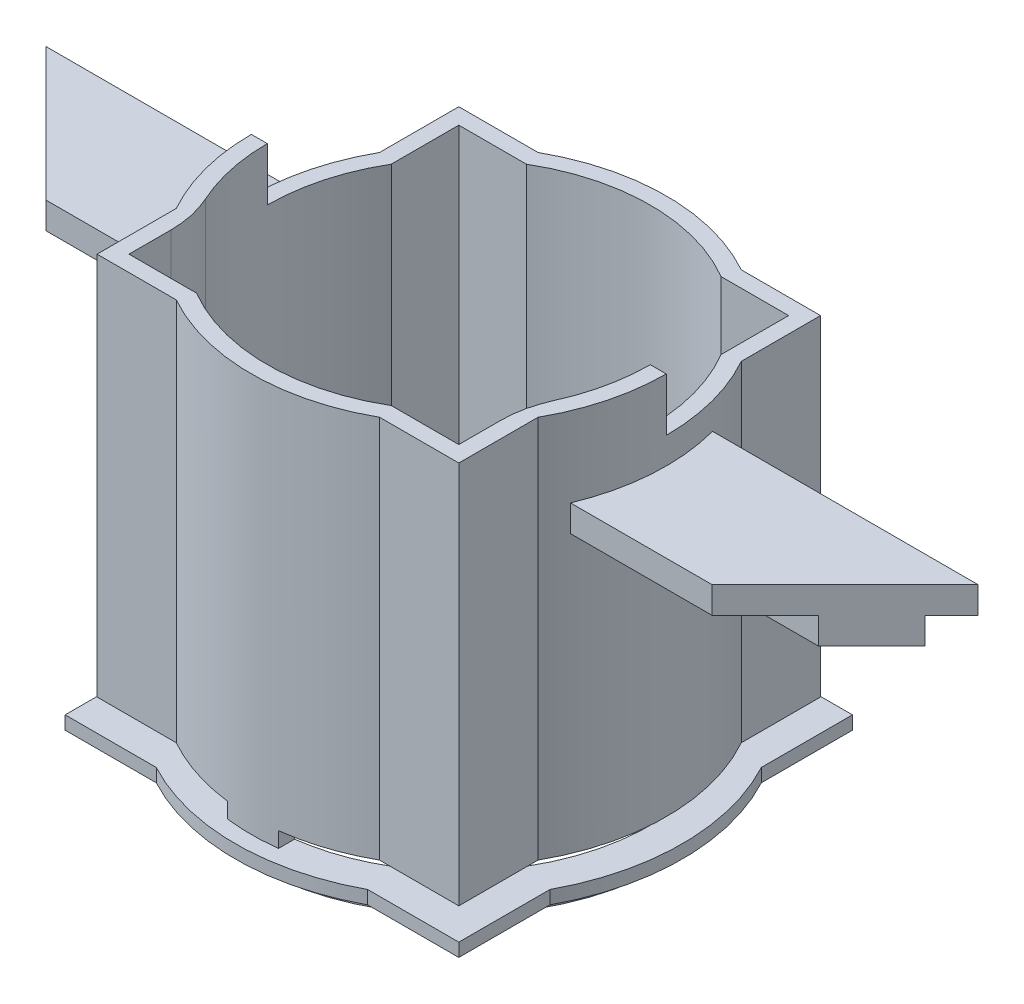
SolidWorks part; units mm, degrees
ref_plane "Front Plane" through (0, 0, 0) normal (0, 0, 1) x (1, 0, 0)
ref_plane "Top Plane" through (0, 0, 0) normal (0, 1, 0) x (1, 0, 0)
ref_plane "Right Plane" through (0, 0, 0) normal (1, 0, 0) x (0, 0, -1)
sketch "Sketch1" plane through (0, 0, 0) normal (0, 1, 0) x (1, 0, 0)
  line L0 (23.2448, 39.37) -> (39.37, 39.37)
  line L1 (-39.37, -39.37) -> (-23.2448, -39.37)
  line L2 (-39.37, -39.37) -> (-39.37, -23.2448)
  line L3 (-39.37, 39.37) -> (-23.2448, 39.37)
  line L4 (39.37, -39.37) -> (39.37, -23.2448)
  line L5 (-39.37, -39.37) -> (39.37, 39.37) construction
  line L6 (-39.37, 39.37) -> (39.37, -39.37) construction
  line L7 (39.37, 23.2448) -> (39.37, 39.37)
  line L8 (-39.37, 23.2448) -> (-39.37, 39.37)
  line L9 (23.2448, -39.37) -> (39.37, -39.37)
  line L10 (24.2633, 43.18) -> (43.18, 43.18)
  line L11 (43.18, 24.2633) -> (43.18, 43.18)
  line L12 (43.18, -43.18) -> (43.18, -24.2633)
  line L13 (24.2633, -43.18) -> (43.18, -43.18)
  line L14 (-43.18, -43.18) -> (-24.2633, -43.18)
  line L15 (-43.18, -43.18) -> (-43.18, -24.2633)
  line L16 (-43.18, 24.2633) -> (-43.18, 43.18)
  line L17 (-43.18, 43.18) -> (-24.2633, 43.18)
  arc A1 (-39.37, 23.2448) -> (-39.37, -23.2448) centre (0, 0) ccw
  arc A2 (23.2448, 39.37) -> (-23.2448, 39.37) centre (0, 0) ccw
  arc A3 (-23.2448, -39.37) -> (23.2448, -39.37) centre (0, 0) ccw
  arc A4 (39.37, -23.2448) -> (39.37, 23.2448) centre (0, 0) ccw
  arc A5 (43.18, -24.2633) -> (43.18, 24.2633) centre (0, 0) ccw
  arc A6 (-24.2633, -43.18) -> (24.2633, -43.18) centre (0, 0) ccw
  arc A7 (-43.18, 24.2633) -> (-43.18, -24.2633) centre (0, 0) ccw
  arc A8 (24.2633, 43.18) -> (-24.2633, 43.18) centre (0, 0) ccw
  point P0 (0, 0)
  dimension "D1" = 78.74
  dimension "D2" = 78.74
  dimension "D3" = 91.44
  dimension "D4" = 3.81
extrude "Boss-Extrude1" add sketch "Sketch1" along normal blind 101.6
sketch "Sketch6" plane through (0, 0, 0) normal (0, 0, 1) x (1, 0, 0)
  line L1 (-56.642, 10.033) -> (-6.096, 10.033)
  line L2 (-56.642, 10.033) -> (-56.642, 6.35)
  line L3 (-56.642, 6.35) -> (-6.096, 6.35)
  line L5 (-43.18, 0) -> (-24.2633, 0) construction
  line L8 (-6.096, 10.033) -> (-6.096, 6.35)
  line L9 (0, 0) -> (0, 21.9448) construction
  line L10 (6.096, 10.033) -> (6.096, 6.35)
  line L11 (56.642, 6.35) -> (6.096, 6.35)
  line L12 (56.642, 10.033) -> (6.096, 10.033)
  line L13 (56.642, 10.033) -> (56.642, 6.35)
  dimension "D3" = 3.683
  dimension "D1" = 6.096
  dimension "D4" = 6.35
extrude "Cut-Extrude4" cut sketch "Sketch6" against normal through all both and the other way through all
ref_plane "Plane1" through (0, 69.85, 0) normal (0, 1, 0) x (1, 0, 0)
sketch "Sketch9" plane through (0, 69.85, 0) normal (0, 1, 0) x (1, 0, 0)
  line L1 (-92.202, -6.35) -> (-49.1213, -6.35)
  line L3 (-104.902, 6.35) -> (-49.1213, 6.35)
  line L7 (-104.902, 6.35) -> (-92.202, -6.35)
  arc A0 (-43.18, 24.2633) -> (-43.18, -24.2633) centre (0, 0) ccw construction
  arc A1 (-49.1213, 6.35) -> (-49.1213, -6.35) centre (0, 0) ccw
  point P0 (0, 0)
  point P2 (-98.552, 0)
  dimension "D1" = 104.902
  dimension "D2" = 45
  dimension "D4" = 12.7
extrude "Boss-Extrude6" add sketch "Sketch9" along normal blind 12.7
sketch "Sketch11" plane through (0, 82.55, 0) normal (0, 1, 0) x (1, 0, 0)
  line L0 (-79.502, -19.05) -> (-79.502, 12.7) construction
  line L1 (-79.502, 12.7) -> (-111.252, 12.7)
  line L2 (-111.252, 12.7) -> (-79.502, -19.05)
  line L3 (-104.902, 6.35) -> (-92.202, -6.35) construction
  line L4 (-49.1213, 6.35) -> (-104.902, 6.35) construction
  line L5 (-92.202, -6.35) -> (-49.1213, -6.35) construction
  line L6 (-79.502, -19.05) -> (-45.72, -19.05)
  line L8 (-47.8741, 12.7) -> (-79.502, 12.7)
  arc A0 (-43.18, 24.2633) -> (-43.18, -24.2633) centre (0, 0) ccw construction
  arc A2 (-47.8741, 12.7) -> (-45.72, -19.05) centre (0, 0) ccw
  dimension "D1" = 6.35
  dimension "D2" = 12.7
extrude "Boss-Extrude8" add sketch "Sketch11" against normal blind 6.35
mirror "Mirror1" about plane through (0, 0, 0) normal (1, 0, 0) of "Boss-Extrude6", "Boss-Extrude8"
sketch "Sketch12" plane through (0, 101.6, 0) normal (0, -1, 0) x (1, 0, 0)
  line L0 (25.2408, -46.99) -> (46.99, -46.99)
  line L1 (46.99, -46.99) -> (46.99, -25.2408)
  line L2 (46.99, 25.2408) -> (46.99, 46.99)
  line L3 (46.99, 46.99) -> (25.2408, 46.99)
  line L4 (-25.2408, 46.99) -> (-46.99, 46.99)
  line L5 (-46.99, 46.99) -> (-46.99, 25.2408)
  line L6 (-46.99, -25.2408) -> (-46.99, -46.99)
  line L7 (-46.99, -46.99) -> (-25.2408, -46.99)
  line L8 (24.2633, -43.18) -> (43.18, -43.18)
  line L9 (43.18, -43.18) -> (43.18, -24.2633)
  line L10 (43.18, 24.2633) -> (43.18, 43.18)
  line L11 (43.18, 43.18) -> (24.2633, 43.18)
  line L12 (-24.2633, 43.18) -> (-43.18, 43.18)
  line L13 (-43.18, 43.18) -> (-43.18, 24.2633)
  line L14 (-43.18, -24.2633) -> (-43.18, -43.18)
  line L15 (-43.18, -43.18) -> (-24.2633, -43.18)
  line L16 (24.2633, -43.18) -> (43.18, -43.18)
  line L17 (43.18, -43.18) -> (43.18, -24.2633)
  line L18 (43.18, 24.2633) -> (43.18, 43.18)
  line L19 (43.18, 43.18) -> (24.2633, 43.18)
  line L20 (-24.2633, 43.18) -> (-43.18, 43.18)
  line L21 (-43.18, 43.18) -> (-43.18, 24.2633)
  line L22 (-43.18, -24.2633) -> (-43.18, -43.18)
  line L23 (-43.18, -43.18) -> (-24.2633, -43.18)
  arc A0 (46.99, -25.2408) -> (46.99, 25.2408) centre (0, 0) ccw
  arc A3 (25.2408, 46.99) -> (-25.2408, 46.99) centre (0, 0) ccw
  arc A4 (-46.99, 25.2408) -> (-46.99, -25.2408) centre (0, 0) ccw
  arc A5 (-25.2408, -46.99) -> (25.2408, -46.99) centre (0, 0) ccw
  arc A7 (-24.2633, -43.18) -> (24.2633, -43.18) centre (0, 0) ccw
  arc A8 (43.18, -24.2633) -> (43.18, 24.2633) centre (0, 0) ccw
  arc A9 (24.2633, 43.18) -> (-24.2633, 43.18) centre (0, 0) ccw
  arc A10 (-43.18, 24.2633) -> (-43.18, -24.2633) centre (0, 0) ccw
  arc A11 (-24.2633, -43.18) -> (24.2633, -43.18) centre (0, 0) ccw
  arc A12 (43.18, -24.2633) -> (43.18, 24.2633) centre (0, 0) ccw
  arc A13 (24.2633, 43.18) -> (-24.2633, 43.18) centre (0, 0) ccw
  arc A14 (-43.18, 24.2633) -> (-43.18, -24.2633) centre (0, 0) ccw
  dimension "D1" = 0
  dimension "D2" = 3.81
extrude "Boss-Extrude9" add sketch "Sketch12" along normal blind 3.175 from surface starting at face at (-28.9674, 6.35, 0)
sketch "Sketch13" plane through (0, 0, 0) normal (0, 0, 1) x (1, 0, 0)
  line L0 (24.2633, 101.6) -> (-24.2633, 101.6) construction
  line L1 (-71.4448, 101.6) -> (67.7277, 101.6)
  line L2 (-71.4448, 101.6) -> (-71.4448, 88.9)
  line L3 (-71.4448, 88.9) -> (67.7277, 88.9)
  line L4 (67.7277, 101.6) -> (67.7277, 88.9)
  dimension "D1" = 12.7
extrude "Cut-Extrude6" cut sketch "Sketch13" against normal through all
fillet "Fillet1" radius 25.4 2 edges at (39.37, 55.8165, 23.2448) (-39.37, 55.8165, 23.2448)
sketch "Sketch16" plane through (0, 6.35, 0) normal (0, 1, 0) x (1, 0, 0)
  line L1 (-19.05, 58.42) -> (19.05, 58.42)
  line L2 (-19.05, 58.42) -> (-19.05, 45.72)
  line L3 (-19.05, 45.72) -> (19.05, 45.72)
  line L4 (19.05, 58.42) -> (19.05, 45.72)
  line L5 (-19.05, 58.42) -> (19.05, 45.72) construction
  line L6 (-19.05, 45.72) -> (19.05, 58.42) construction
  arc A0 (23.2448, 39.37) -> (-23.2448, 39.37) centre (0, 0) ccw construction
  point P0 (0, 52.07)
  dimension "D1" = 12.7
  dimension "D2" = 38.1
extrude "Boss-Extrude13" add sketch "Sketch16" against normal blind 3.175
sketch "Sketch18" plane through (0, 6.35, 0) normal (0, 1, 0) x (1, 0, 0)
  line L0 (-19.05, 58.42) -> (-19.05, 49.8222) construction
  line L1 (19.05, 58.42) -> (-19.05, 58.42) construction
  circle A0 centre (-12.7, 52.07) radius 3.175
  dimension "D2" = 6.35
  dimension "D1" = 6.35
  dimension "D3" = 6.35
extrude "Boss-Extrude14" add sketch "Sketch18" along normal blind 6.35
mirror "Mirror2" about plane through (0, 0, 0) normal (1, 0, 0) of "Boss-Extrude14"
equation "\"tightTol\" = 0.005in"
equation "\"normTol\"= 0.01in"
equation "\"looseTol\"= 0.02in"
equation "\"D1@Sketch6\" = 0.250000in - \"normTol\""
equation "\"D3@Sketch6\"=\"looseTol\"+0.125000in"
